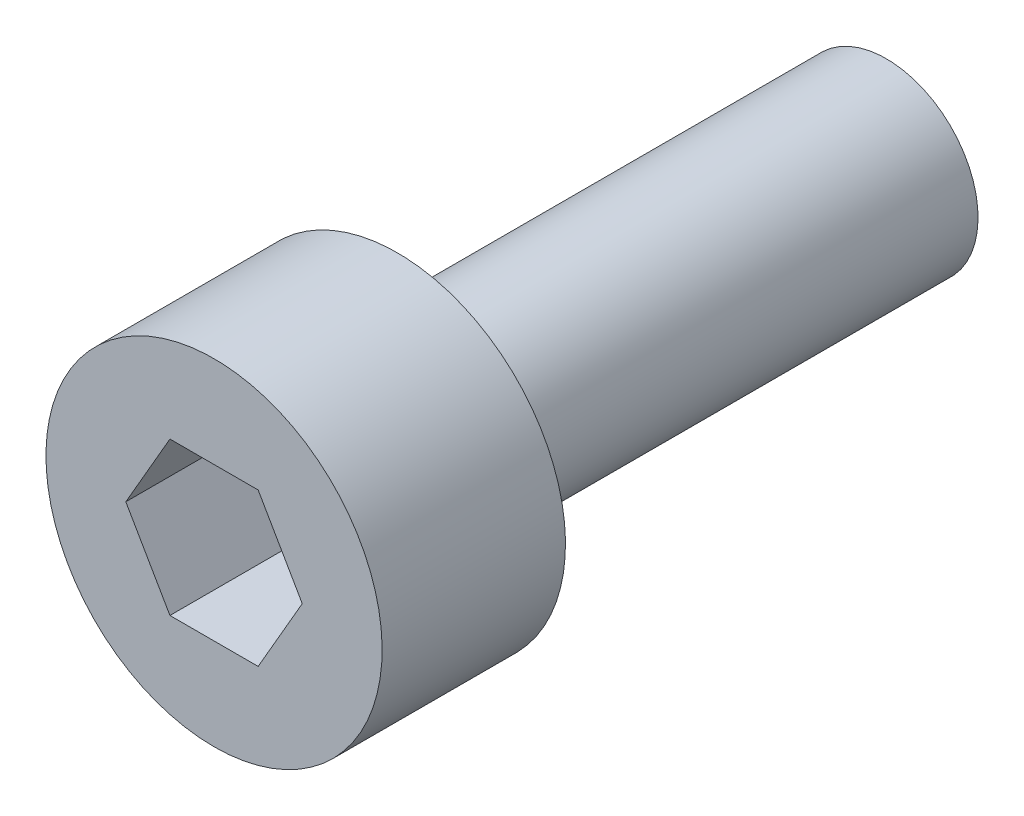
SolidWorks part; units mm, degrees
material "AISI 304"
ref_plane "Front Plane" through (0, 0, 0) normal (0, 0, 1) x (1, 0, 0)
ref_plane "Top Plane" through (0, 0, 0) normal (0, 1, 0) x (1, 0, 0)
ref_plane "Right Plane" through (0, 0, 0) normal (1, 0, 0) x (0, 0, -1)
ref_axis "Axis1" through (0, 0, -52.8182) along (0, 0, 1)
ref_axis "Axis2" through (0, -15.5981, 0) along (0, 1, 0)
ref_axis "Axis3" through (-12.2581, 0, 0) along (1, 0, 0)
sketch "Sketch1" plane through (0, 0, 0) normal (1, 0, 0) x (0, 0, -1)
  line L0 (-3, 0) -> (-3, 2.75)
  line L1 (-3, 2.75) -> (0, 2.75)
  line L2 (0, 2.75) -> (0, 1.5)
  line L3 (0, 1.5) -> (8, 1.5)
  line L4 (8, 1.5) -> (8, 0)
  line L5 (8, 0) -> (-3, 0)
  line L6 (-5.5849, 0) -> (13.8966, 0) construction
  dimension "D1" = 3
  dimension "D2" = 5.5
  dimension "D3" = 3
  dimension "Length" = 8
revolve "Revolve1" add sketch "Sketch1" angle 360 about L6
cosmetic thread "Cosmetic Thread1" parameters "D1"=8, "D2"=2.439
sketch "Sketch2" plane through (0, 0, 3) normal (0, 0, 1) x (1, 0, 0)
  line L1 (0.7217, -1.25) -> (1.4434, 0)
  line L2 (1.4434, 0) -> (0.7217, 1.25)
  line L3 (0.7217, 1.25) -> (-0.7217, 1.25)
  line L4 (-0.7217, 1.25) -> (-1.4434, 0)
  line L5 (-1.4434, 0) -> (-0.7217, -1.25)
  line L6 (-0.7217, -1.25) -> (0.7217, -1.25)
  circle A0 centre (0, 0) radius 1.25 construction
  dimension "D1" = 2.5
extrude "Cut-Extrude1" cut sketch "Sketch2" against normal blind 2
